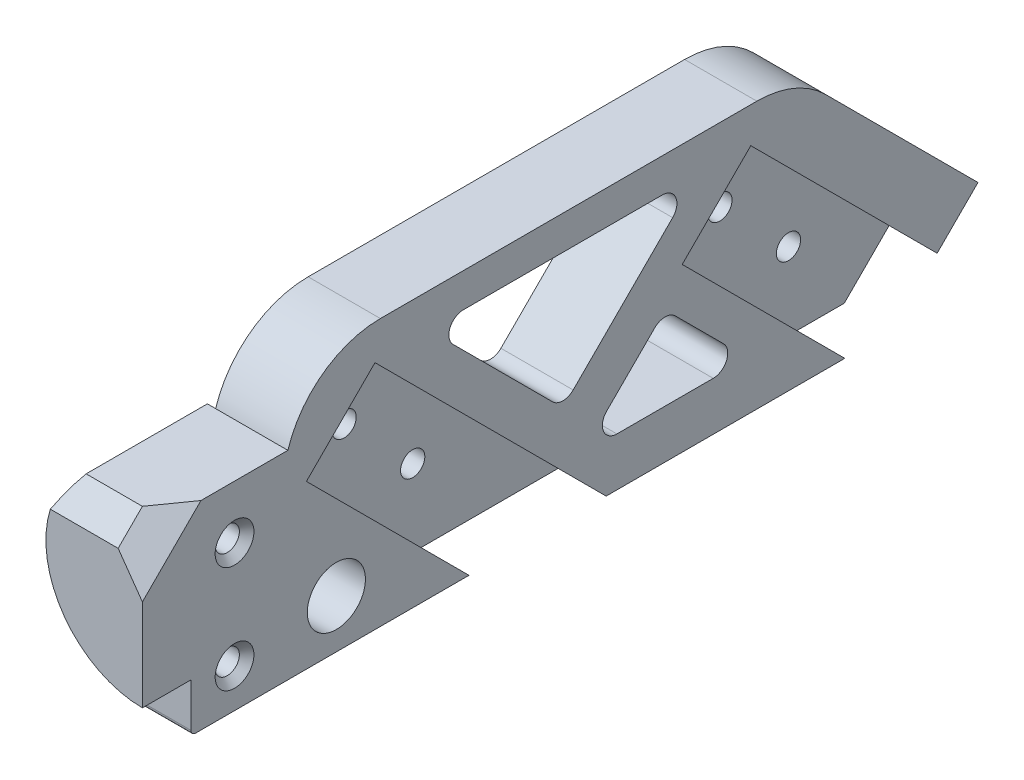
SolidWorks part; units mm, degrees
ref_plane "前视基准面" through (0, 0, 0) normal (0, 0, 1) x (1, 0, 0)
ref_plane "上视基准面" through (0, 0, 0) normal (0, 1, 0) x (1, 0, 0)
ref_plane "右视基准面" through (0, 0, 0) normal (1, 0, 0) x (0, 0, -1)
sketch "草图1" plane through (0, 0, 0) normal (0, 0, 1) x (1, 0, 0)
  line L0 (16.7033, 11) -> (-16.7033, 11)
  arc A0 (-16.7033, 11) -> (16.7033, 11) centre (0, 0) ccw
  dimension "D1" = 40
  dimension "D2" = 11
extrude "凸台-拉伸1" add sketch "草图1" along normal blind 21
sketch "草图2" plane through (0, 0, 21) normal (0, 0, 1) x (1, 0, 0)
  line L1 (10, -10) -> (-10, -10)
  line L2 (10, -10) -> (10, 10)
  line L3 (10, 10) -> (-10, 10)
  line L4 (-10, -10) -> (-10, 10)
  line L5 (10, -10) -> (-10, 10) construction
  line L6 (10, 10) -> (-10, -10) construction
  point P0 (0, 0)
  dimension "D1" = 20
  dimension "D2" = 20
extrude "切除-拉伸1" cut sketch "草图2" against normal blind 10
sketch "草图3" plane through (0, 0, 0) normal (0, 0, -1) x (-1, 0, 0)
  line L1 (16.7033, 11) -> (-16.7033, 11)
  line L2 (16.7033, 11) -> (-16.7033, 11)
  circle A0 centre (0, 0) radius 25
  arc A1 (-16.7033, 11) -> (16.7033, 11) centre (0, 0) ccw
  arc A2 (-16.7033, 11) -> (16.7033, 11) centre (0, 0) ccw
  dimension "D2" = 50
  dimension "D1" = 0
extrude "凸台-拉伸2" add sketch "草图3" against normal blind 2
sketch "草图4" plane through (0, 0, 11) normal (0, 0, 1) x (1, 0, 0)
  line L4 (-10, 10) -> (-10, -10)
  line L5 (-10, -10) -> (10, -10)
  line L6 (10, -10) -> (10, 10)
  line L7 (10, 10) -> (-10, 10)
  line L8 (-10, 10) -> (-10, -10)
  line L9 (-10, -10) -> (10, -10)
  line L10 (10, -10) -> (10, 10)
  line L11 (10, 10) -> (-10, 10)
  dimension "D1" = 0
extrude "切除-拉伸2" cut sketch "草图4" against normal blind 20
sketch "草图5" plane through (0, 11, 0) normal (0, 1, 0) x (1, 0, 0)
  line L1 (-33.8348, 26.2279) -> (33.8348, 26.2279)
  line L2 (-33.8348, 26.2279) -> (-33.8348, -26.2279)
  line L3 (-33.8348, -26.2279) -> (33.8348, -26.2279)
  line L4 (33.8348, 26.2279) -> (33.8348, -26.2279)
  line L5 (-33.8348, 26.2279) -> (33.8348, -26.2279) construction
  line L6 (-33.8348, -26.2279) -> (33.8348, 26.2279) construction
  point P0 (0, 0)
extrude "切除-拉伸3" cut sketch "草图5" along normal blind 22
sketch "草图6" plane through (0, 0, 0) normal (0, 1, 0) x (1, 0, 0)
  line L0 (-20, -21) -> (20, -21) construction
  line L1 (20, -21) -> (20, -2) construction
  circle A0 centre (0, -13) radius 2.55
  dimension "D1" = 5.1
  dimension "D2" = 8
  dimension "D3" = 20
extrude "切除-拉伸4" [suppressed] cut sketch "草图6" against normal blind 22
pattern_circular "阵列(圆周)1" [suppressed] count 4 over 360 of bodies 111
sketch "草图7" plane through (0, 0, 21) normal (0, 0, 1) x (1, 0, 0)
  line L0 (-3.3541, 11) -> (-16.7033, 11)
  line L1 (16.7033, 11) -> (-16.7033, 11)
  line L5 (16.7033, 11) -> (-16.7033, 11)
  arc A0 (-3.3541, 11) -> (3.3541, 11) centre (0, 0) ccw
  arc A1 (-16.7033, 11) -> (16.7033, 11) centre (0, 0) ccw
  arc A5 (-16.7033, 11) -> (16.7033, 11) centre (0, 0) ccw
  dimension "22.5" = 23
  dimension "D1" = 0
extrude "凸台-拉伸3" [suppressed] add sketch "草图7" along normal blind 1
sketch "草图8" [suppressed] plane through (0, 0, 21) normal (0, 0, 1) x (1, 0, 0)
  circle A0 centre (0, 20) radius 12
  dimension "D2" = 24
  dimension "D1" = 20
extrude "切除-拉伸5" [suppressed] cut sketch "草图8" against normal up to surface (1 mm away) up to face at (0, 0, 21)
fillet "圆角1" [suppressed] radius 3
sketch "草图9" [suppressed] plane through (0, 0, 21) normal (0, 0, 1) x (1, 0, 0)
  line L2 (16.7033, 11) -> (7.9373, 11)
  line L3 (-7.9373, 11) -> (-16.7033, 11)
  line L4 (16.7033, 11) -> (7.9373, 11)
  line L5 (-7.9373, 11) -> (-16.7033, 11)
  arc A4 (7.9373, 11) -> (8.4758, 7.7725) centre (10.6868, 9.8001) ccw
  arc A5 (-8.4758, 7.7725) -> (8.4758, 7.7725) centre (0, 0) ccw
  arc A6 (-8.4758, 7.7725) -> (-7.9373, 11) centre (-10.6868, 9.8001) ccw
  arc A7 (-16.7033, 11) -> (16.7033, 11) centre (0, 0) ccw
  arc A8 (7.9373, 11) -> (8.4758, 7.7725) centre (10.6868, 9.8001) ccw
  arc A9 (-8.4758, 7.7725) -> (8.4758, 7.7725) centre (0, 0) ccw
  arc A10 (-8.4758, 7.7725) -> (-7.9373, 11) centre (-10.6868, 9.8001) ccw
  arc A11 (-16.7033, 11) -> (16.7033, 11) centre (0, 0) ccw
  dimension "D1" = 0
extrude "凸台-拉伸4" [suppressed] add sketch "草图9" along normal blind 1
sketch "草图10" plane through (0, 0, 21) normal (0, 0, 1) x (1, 0, 0)
  line L1 (16.7033, 11) -> (-16.7033, 11)
  line L2 (16.7033, 11) -> (-16.7033, 11)
  arc A1 (-16.7033, 11) -> (16.7033, 11) centre (0, 0) ccw
  arc A2 (-16.7033, 11) -> (16.7033, 11) centre (0, 0) ccw
  dimension "D1" = 0
extrude "凸台-拉伸5" add sketch "草图10" along normal blind 1
sketch "草图11" plane through (0, 0, 21) normal (0, 0, -1) x (-1, 0, 0)
  line L0 (-10, 10) -> (10, 10) construction
  line L1 (-3, 24) -> (3, 24)
  line L2 (-3, 24) -> (-3, -4)
  line L3 (-3, -4) -> (3, -4)
  line L4 (3, 24) -> (3, -4)
  line L5 (-3, 24) -> (3, -4) construction
  line L6 (-3, -4) -> (3, 24) construction
  point P0 (0, 10)
  dimension "D1" = 6
  dimension "D2" = 28
extrude "切除-拉伸6" [suppressed] cut sketch "草图11" against normal blind 1
sketch "草图12" plane through (0, 0, 21) normal (0, 0, -1) x (-1, 0, 0)
  line L11 (10, 10) -> (-10, 10)
  line L12 (-10, 10) -> (-10, -10)
  line L13 (-10, -10) -> (10, -10)
  line L14 (10, -10) -> (10, 10)
  line L19 (10, 10) -> (-10, 10)
  line L20 (-10, 10) -> (-10, -10)
  line L21 (-10, -10) -> (10, -10)
  line L22 (10, -10) -> (10, 10)
  dimension "D1" = 0
extrude "凸台-拉伸6" [suppressed] add sketch "草图12" along normal blind 1
sketch "草图13" [suppressed] plane through (0, 0, 20) normal (0, 0, -1) x (-1, 0, 0)
  circle A0 centre (0, 0) radius 2.5
  dimension "D1" = 5
extrude "切除-拉伸7" [suppressed] cut sketch "草图13" against normal blind 44
sketch "草图14" [suppressed] plane through (0, 0, 22) normal (0, 0, 1) x (1, 0, 0)
  line L1 (-2.5, 5) -> (2.5, 5)
  line L2 (-2.5, 5) -> (-2.5, 0)
  line L3 (-2.5, 0) -> (2.5, 0)
  line L4 (2.5, 5) -> (2.5, 0)
  line L5 (-2.5, 5) -> (2.5, 0) construction
  line L6 (-2.5, 0) -> (2.5, 5) construction
  circle A0 centre (0, 0) radius 2.5 construction
  point P0 (0, 2.5)
  dimension "D1" = 5
extrude "切除-拉伸8" [suppressed] cut sketch "草图14" against normal blind 1
sketch "草图15" [suppressed] plane through (0, 0, 22) normal (0, 0, 1) x (1, 0, 0)
  line L0 (2.5, 5) -> (-2.5, 5) construction
  circle A0 centre (0, 5) radius 2.5
extrude "切除-拉伸9" [suppressed] cut sketch "草图15" against normal blind 1
sketch "草图16" [suppressed] plane through (0, 0, 22) normal (0, 0, 1) x (1, 0, 0)
  line L0 (16.7033, 11) -> (-16.7033, 11) construction
  line L1 (-2.5, 5) -> (2.5, 5)
  line L2 (-2.5, 5) -> (-2.5, 11)
  line L3 (-2.5, 11) -> (2.5, 11)
  line L4 (2.5, 5) -> (2.5, 11)
  dimension "D1" = 5
extrude "切除-拉伸10" [suppressed] cut sketch "草图16" against normal blind 1
sketch "草图17" [suppressed] plane through (0, 0, 21) normal (0, 0, 1) x (1, 0, 0)
  circle A0 centre (0, 7) radius 2.5
  dimension "D1" = 5
  dimension "D2" = 7
extrude "切除-拉伸11" [suppressed] cut sketch "草图17" against normal blind 6
fillet "圆角2" [suppressed] radius 0.5
fillet "圆角3" [suppressed] radius 1
sketch "草图18" plane through (0, 0, 2) normal (0, 0, 1) x (1, 0, 0)
  line L2 (-16.7033, 11) -> (-22.4499, 11)
  line L3 (22.4499, 11) -> (16.7033, 11)
  line L4 (-16.7033, 11) -> (-22.4499, 11)
  line L5 (22.4499, 11) -> (16.7033, 11)
  arc A2 (-22.4499, 11) -> (22.4499, 11) centre (0, 0) ccw
  arc A3 (-16.7033, 11) -> (16.7033, 11) centre (0, 0) ccw
  arc A4 (-22.4499, 11) -> (22.4499, 11) centre (0, 0) ccw
  arc A5 (-16.7033, 11) -> (16.7033, 11) centre (0, 0) ccw
  dimension "D1" = 0
extrude "切除-拉伸12" cut sketch "草图18" against normal blind 6
sketch "草图19" plane through (0, 0, 0) normal (0, 0, -1) x (-1, 0, 0)
  line L1 (16.7033, 11) -> (-16.7033, 11)
  line L2 (16.7033, 11) -> (-16.7033, 11)
  arc A1 (-16.7033, 11) -> (16.7033, 11) centre (0, 0) ccw
  arc A4 (-16.7033, 11) -> (16.7033, 11) centre (0, 0) ccw
  dimension "D1" = 0
extrude "切除-拉伸13" cut sketch "草图19" against normal blind 2
sketch "草图20" [suppressed] plane through (0, 11, 0) normal (0, 1, 0) x (1, 0, 0)
  line L1 (-2.55, -13) -> (2.55, -13)
  line L2 (-2.55, -13) -> (-2.55, 0.9444)
  line L3 (-2.55, 0.9444) -> (2.55, 0.9444)
  line L4 (2.55, -13) -> (2.55, 0.9444)
  circle A0 centre (0, -13) radius 2.55 construction
  dimension "D1" = 5.1
extrude "切除-拉伸14" [suppressed] cut sketch "草图20" against normal blind 2
sketch "草图21" plane through (0, 0, 21) normal (0, 0, -1) x (-1, 0, 0)
  line L4 (10, -10) -> (10, 10)
  line L5 (10, 10) -> (-10, 10)
  line L6 (-10, 10) -> (-10, -10)
  line L7 (-10, -10) -> (10, -10)
  line L8 (10, -10) -> (10, 10)
  line L9 (10, 10) -> (-10, 10)
  line L10 (-10, 10) -> (-10, -10)
  line L11 (-10, -10) -> (10, -10)
  dimension "D1" = 0
extrude "凸台-拉伸7" add sketch "草图21" along normal up to surface (19 mm away) up to face at (0, -4.5, 2)
sketch "草图22" plane through (0, 0, 2) normal (0, 0, -1) x (-1, 0, 0)
  line L1 (-15, -10) -> (15, -10)
  line L2 (-15, -10) -> (-15, -30)
  line L3 (-15, -30) -> (15, -30)
  line L4 (15, -10) -> (15, -30)
  line L5 (-15, -10) -> (15, -30) construction
  line L6 (-15, -30) -> (15, -10) construction
  arc A0 (-16.7033, 11) -> (16.7033, 11) centre (0, 0) ccw construction
  point P0 (0, -20)
  dimension "D1" = 30
  dimension "D2" = 20
extrude "凸台-拉伸8" add sketch "草图22" against normal blind 10
sketch "草图23" plane through (0, 0, 2) normal (0, 0, -1) x (-1, 0, 0)
  line L4 (-15, -13.2288) -> (-15, -30)
  line L5 (-15, -30) -> (15, -30)
  line L6 (15, -30) -> (15, -13.2288)
  line L7 (16.7033, 11) -> (-16.7033, 11)
  line L8 (-15, -13.2288) -> (-15, -30)
  line L9 (-15, -30) -> (15, -30)
  line L10 (15, -30) -> (15, -13.2288)
  line L11 (16.7033, 11) -> (-16.7033, 11)
  arc A2 (-16.7033, 11) -> (-15, -13.2288) centre (0, 0) ccw
  arc A3 (15, -13.2288) -> (16.7033, 11) centre (0, 0) ccw
  arc A4 (-16.7033, 11) -> (-15, -13.2288) centre (0, 0) ccw
  arc A5 (15, -13.2288) -> (16.7033, 11) centre (0, 0) ccw
  dimension "D1" = 0
extrude "凸台-拉伸9" add sketch "草图23" along normal blind 10
sketch "草图24" plane through (0, 0, -8) normal (0, 0, -1) x (-1, 0, 0)
  line L1 (-15, -30) -> (15, -30)
  line L2 (-15, -30) -> (-15, 20)
  line L3 (-15, 20) -> (15, 20)
  line L4 (15, -30) -> (15, 20)
  dimension "D1" = 30
  dimension "D2" = 50
extrude "凸台-拉伸10" add sketch "草图24" along normal blind 160
sketch "草图26" plane through (-15, 0, 0) normal (-1, 0, 0) x (0, 0, 1)
  line L0 (-8, -13.2288) -> (-8, 11) construction
  circle A0 centre (-107, 0) radius 2.5
  circle A1 centre (-29.5, 0) radius 2.5
  dimension "D1" = 5
  dimension "D2" = 99
  dimension "D3" = 77.5
extrude "切除-拉伸15" cut sketch "草图26" against normal blind 50
sketch "草图27" plane through (0, 0, 0) normal (1, 0, 0) x (0, 0, -1)
  line L0 (96.3934, 10.6066) -> (145.8909, -38.8909)
  line L1 (-12, -30) -> (168, -30) construction
  line L2 (18.8934, 10.6066) -> (68.3909, -38.8909)
  circle A0 centre (107, 0) radius 2.5 construction
  dimension "D1" = 15
  dimension "D2" = 45
  dimension "D3" = 70
extrude "切除-拉伸-薄壁1" cut sketch "草图27" against normal blind 10 and the other way blind 10 thin thin type mid plane wall 20
sketch "草图28" plane through (0, 20, 0) normal (0, 1, 0) x (1, 0, 0)
  line L4 (-15, 8) -> (15, 8)
  line L5 (15, 8) -> (15, 168)
  line L6 (15, 168) -> (-15, 168)
  line L7 (-15, 168) -> (-15, 8)
  line L8 (-15, 8) -> (15, 8)
  line L9 (15, 8) -> (15, 168)
  line L10 (15, 168) -> (-15, 168)
  line L11 (-15, 168) -> (-15, 8)
  dimension "D1" = 0
extrude "凸台-拉伸11" add sketch "草图28" along normal blind 5
sketch "草图29" plane through (-15, 0, 0) normal (-1, 0, 0) x (0, 0, 1)
  circle A0 centre (3, 0) radius 2.5
  circle A1 centre (3, -22) radius 2.5
  dimension "D1" = 5
  dimension "D2" = 5
extrude "切除-拉伸16" cut sketch "草图29" against normal blind 60 and the other way blind 25
sketch "草图30" plane through (-15, 0, 0) normal (-1, 0, 0) x (0, 0, 1)
  line L0 (-113, 25) -> (-168, -30)
  line L1 (-168, 25) -> (-8, 25) construction
  line L2 (-168, -30) -> (-168, 25) construction
  line L3 (-168, -30) -> (-168, 25)
  line L4 (-168, 25) -> (-113, 25)
  dimension "D1" = 45
  dimension "D2" = 55
extrude "切除-拉伸17" cut sketch "草图30" against normal blind 60
sketch "草图31" plane through (0, 0, 0) normal (1, 0, 0) x (0, 0, -1)
  line L0 (92.4731, 18) -> (64.7145, -9.7586)
  line L1 (64.7145, -9.7586) -> (36.9558, 18)
  line L2 (36.9558, 18) -> (92.4731, 18)
  line L3 (8, 25) -> (113, 25) construction
  line L4 (89.3223, 3.5355) -> (103.4645, 17.6777) construction
  line L6 (25.9645, 17.6777) -> (73.6421, -30) construction
  dimension "D1" = 7
  dimension "D2" = 8
  dimension "D3" = 90
  dimension "D4" = 8
extrude "切除-拉伸18" cut sketch "草图31" against normal blind 60 and the other way blind 60
sketch "草图32" plane through (0, 0, 0) normal (1, 0, 0) x (0, 0, -1)
  line L0 (85.7868, -2.8284) -> (102.9584, -20)
  line L1 (102.9584, -20) -> (68.6152, -20)
  line L2 (68.6152, -20) -> (85.7868, -2.8284)
  line L3 (89.3223, 3.5355) -> (122.8579, -30) construction
  line L4 (-12, -30) -> (168, -30) construction
  line L5 (92.4731, 18) -> (64.7145, -9.7586) construction
  dimension "D1" = 7
  dimension "D2" = 10
  dimension "D3" = 10
extrude "切除-拉伸19" cut sketch "草图32" against normal blind 60 and the other way blind 60
fillet "圆角4" radius 3 6 edges at (0, -2.8284, -85.7868) (0, -20, -102.9584) (0, -20, -68.6152) (0, 18, -36.9558) (0, 18, -92.4731) (0, -9.7586, -64.7145)
sketch "草图33" plane through (0, 0, 0) normal (1, 0, 0) x (0, 0, -1)
  line L0 (-12, -30) -> (168, -30) construction
  line L1 (-12, -13.2288) -> (-12, -30) construction
  circle A0 centre (18, -20) radius 6
  dimension "D1" = 12
  dimension "D2" = 10
  dimension "D3" = 30
extrude "切除-拉伸20" cut sketch "草图33" against normal blind 60 and the other way blind 60
sketch "草图34" plane through (-15, 0, 0) normal (-1, 0, 0) x (0, 0, 1)
  line L0 (-150.3223, -12.3223) -> (-132.6447, -30)
  line L1 (-168, -30) -> (-113, 25) construction
  line L2 (12, -30) -> (-168, -30) construction
  line L3 (-132.6447, -30) -> (-168, -30)
  line L4 (-168, -30) -> (-150.3223, -12.3223)
  dimension "D1" = 45
  dimension "D2" = 25
extrude "切除-拉伸21" cut sketch "草图34" against normal blind 60
fillet "圆角5" radius 20 1 edges at (0, 25, -113)
sketch "草图35" plane through (-15, 0, 0) normal (-1, 0, 0) x (0, 0, 1)
  circle A0 centre (-29.5, 0) radius 2.5 construction
  circle A1 centre (-107, 0) radius 2.5 construction
  circle A2 centre (-29.5, 0) radius 2.5
  circle A3 centre (-107, 0) radius 2.5
  circle A4 centre (-121.1421, -14.1421) radius 2.5
  circle A5 centre (-43.6421, -14.1421) radius 2.5
  dimension "D1" = 2
extrude "切除-拉伸22" cut sketch "草图35" against normal blind 60
fillet "圆角6" radius 20 1 edges at (0, 25, -8)
sketch "草图36" plane through (0, 0, 0) normal (1, 0, 0) x (0, 0, -1)
  line L1 (-64.6972, -126.234) -> (192.7695, -126.234)
  line L2 (-64.6972, -126.234) -> (-64.6972, 60.9918)
  line L3 (-64.6972, 60.9918) -> (192.7695, 60.9918)
  line L4 (192.7695, -126.234) -> (192.7695, 60.9918)
  line L5 (-64.6972, -126.234) -> (192.7695, 60.9918) construction
  line L6 (-64.6972, 60.9918) -> (192.7695, -126.234) construction
  point P0 (64.0362, -32.6211)
extrude "切除-拉伸23" cut sketch "草图36" against normal blind 82
sketch "草图37" plane through (0, 0, 0) normal (-1, 0, 0) x (0, 0, 1)
  line L15 (-11.8223, 3.5355) -> (-45.3579, -30)
  line L16 (-45.3579, -30) -> (12, -30)
  line L17 (12, -30) -> (12, -20)
  line L18 (12, -20) -> (22, -20)
  line L19 (22, -20) -> (22, 11)
  line L20 (22, 11) -> (-8, 11)
  line L21 (-27.0788, 25) -> (-104.7157, 25)
  line L22 (-118.8579, 19.1421) -> (-150.3223, -12.3223)
  line L23 (-150.3223, -12.3223) -> (-141.8934, -20.7513)
  line L24 (-141.8934, -20.7513) -> (-103.4645, 17.6777)
  line L25 (-103.4645, 17.6777) -> (-89.3223, 3.5355)
  line L26 (-89.3223, 3.5355) -> (-122.8579, -30)
  line L27 (-122.8579, -30) -> (-73.6421, -30)
  line L28 (-73.6421, -30) -> (-25.9645, 17.6777)
  line L29 (-25.9645, 17.6777) -> (-11.8223, 3.5355)
  line L30 (-11.8223, 3.5355) -> (-45.3579, -30)
  line L31 (-45.3579, -30) -> (12, -30)
  line L32 (12, -30) -> (12, -20)
  line L33 (12, -20) -> (22, -20)
  line L34 (22, -20) -> (22, 11)
  line L35 (22, 11) -> (-8, 11)
  line L36 (-27.0788, 25) -> (-104.7157, 25)
  line L37 (-118.8579, 19.1421) -> (-150.3223, -12.3223)
  line L38 (-150.3223, -12.3223) -> (-141.8934, -20.7513)
  line L39 (-141.8934, -20.7513) -> (-103.4645, 17.6777)
  line L40 (-103.4645, 17.6777) -> (-89.3223, 3.5355)
  line L41 (-89.3223, 3.5355) -> (-122.8579, -30)
  line L42 (-122.8579, -30) -> (-73.6421, -30)
  line L43 (-73.6421, -30) -> (-25.9645, 17.6777)
  line L44 (-25.9645, 17.6777) -> (-11.8223, 3.5355)
  arc A2 (-8, 11) -> (-27.0788, 25) centre (-27.0788, 5) ccw
  arc A3 (-104.7157, 25) -> (-118.8579, 19.1421) centre (-104.7157, 5) ccw
  arc A4 (-8, 11) -> (-27.0788, 25) centre (-27.0788, 5) ccw
  arc A5 (-104.7157, 25) -> (-118.8579, 19.1421) centre (-104.7157, 5) ccw
  dimension "D1" = 0
extrude "切除-拉伸24" cut sketch "草图37" against normal blind 0.1
mirror "镜向1" about plane through (0.1, 5, -27.0788) normal (-1, 0, 0) of bodies 142
delete or keep bodies "实体-删除/保留 1" type delete bodies bodies 142
chamfer "倒角1" distance 1.5 angle 45 2 edges at (0.1, -22, 5.5) (0.1, 0, 5.5)
fillet "圆角7" radius 1 2 edges at (-14.8, -19.5, 3) (-19.7924, -0.5531, 5.438)
fillet "圆角8" radius 1 2 edges at (-7.35, -30, 12) (-14.8, -30, -60.3223)
chamfer "倒角2" distance 5 angle 45 1 edges at (-8.2016, 11, 22)
chamfer "倒角3" distance 5 angle 45 1 edges at (0.1, 8.5, 19.5)
